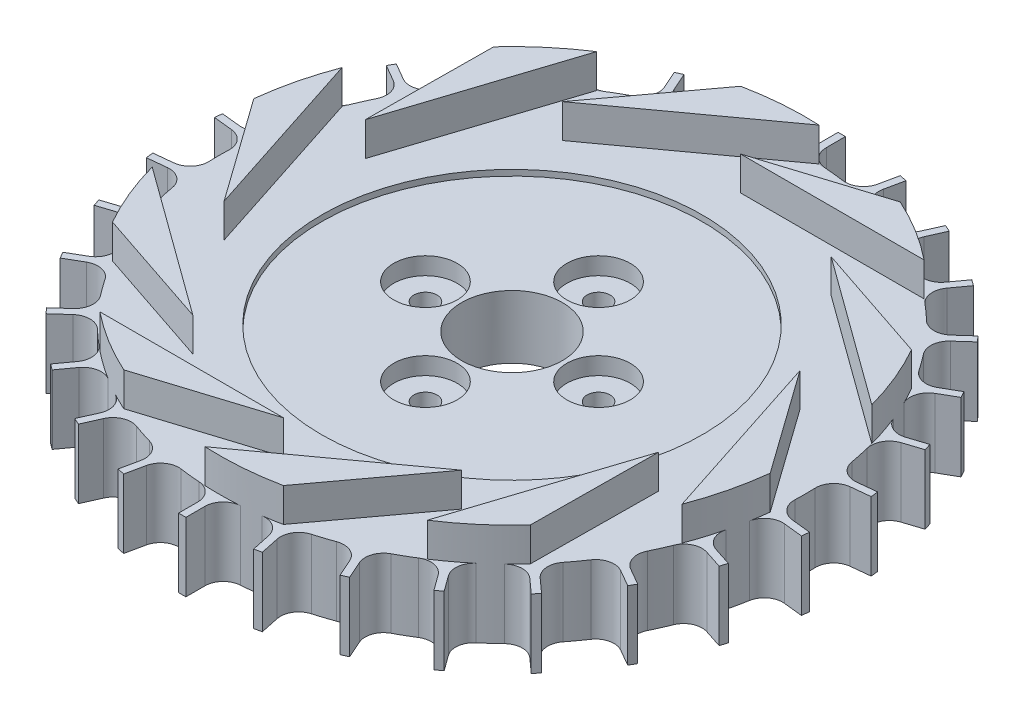
SolidWorks part; units mm, degrees
material "6061-T6 (SS)"
ref_plane "Front Plane" through (0, 0, 0) normal (0, 0, 1) x (1, 0, 0)
ref_plane "Top Plane" through (0, 0, 0) normal (0, 1, 0) x (1, 0, 0)
ref_plane "Right Plane" through (0, 0, 0) normal (1, 0, 0) x (0, 0, -1)
sketch "Sketch1" plane through (0, 0, 0) normal (1, 0, 0) x (0, 0, -1)
  line L0 (0, 26.2631) -> (0, -3.7705) construction
  line L1 (0, -3.7705) -> (-50.8, -3.7705)
  line L2 (-50.8, -3.7705) -> (-50.8, 8.1675)
  line L3 (-33.0001, 8.1675) -> (-50.8, 8.1675)
  line L4 (-33.0001, 8.1675) -> (-33.0001, 7.1515)
  line L5 (-33.0001, 7.1515) -> (0, 7.1515)
  line L6 (0, 7.1515) -> (0, -3.7705)
  dimension "D1" = 33.0001
  dimension "D2" = 50.8
  dimension "D3" = 1.016
  dimension "D4" = 11.938
revolve "Revolve1" add sketch "Sketch1" angle 360 about L0
sketch "Sketch2" plane through (0, 8.1675, 0) normal (0, 1, 0) x (1, 0, 0)
  line L8 (0, 39.6001) -> (19.9397, 39.6001) construction
  line L9 (0, 39.6001) -> (21.0453, 46.2356)
  line L10 (0, 39.6001) -> (31.8194, 39.6001)
  circle A0 centre (0, 0) radius 50.8 construction
  arc A3 (21.0453, 46.2356) -> (31.8194, 39.6001) centre (0, 0) cw
  circle A5 centre (0, 0) radius 33.0001 construction
  circle A7 centre (0, 0) radius 39.6001 construction
  point P9 (-2.4416, -40.4611)
  dimension "D1" = 66.0001
  dimension "D2" = 79.2001
  dimension "D3" = 17.5
extrude "Boss-Extrude1" add sketch "Sketch2" along normal blind 5.842
pattern_circular "CirPattern1" count 10 over 360 about axis through (0, 8.1675, 0) along (0, 1, 0) of "Boss-Extrude1"
ref_plane "Plane1" through (0, 0, 49.53) normal (0, 0, 1) x (1, 0, 0)
sketch "Sketch3" plane through (0, 0, 49.53) normal (0, 0, 1) x (1, 0, 0)
  line L0 (0, 0) -> (0, 9.7621) construction
  line L1 (0, -9.779) -> (0, 9.779) construction
  line L6 (-50.8, -3.7705) -> (50.8, -3.7705) construction
  line L13 (10.1506, 8.1675) -> (23.2763, 8.1675) construction
  line L14 (-0.635, -3.7705) -> (0.635, -3.7705)
  line L15 (-0.635, -3.7705) -> (-0.635, 8.1675)
  line L16 (-0.635, 8.1675) -> (0.635, 8.1675)
  line L17 (0.635, -3.7705) -> (0.635, 8.1675)
  point P11 (0, 8.1675)
  dimension "D1" = 1.27
extrude "Boss-Extrude2" add sketch "Sketch3" along normal blind 7.62 and the other way blind 0.254
fillet "Fillet1" radius 3.175 2 edges at (-0.635, 2.1985, 50.796) (0.635, 2.1985, 50.796)
pattern_circular "CirPattern16" count 30 over 360 about axis through (0, -3.7705, 0) along (0, 1, 0) of "Boss-Extrude2", "Fillet1"
sketch "Sketch4" plane through (0, 7.1515, 0) normal (0, 1, 0) x (1, 0, 0)
  circle A0 centre (0, 0) radius 8.7312
  dimension "D1" = 17.4625
extrude "Cut-Extrude1" cut sketch "Sketch4" against normal up to next
sketch "Sketch5" plane through (0, -3.7705, 0) normal (0, -1, 0) x (-1, 0, 0)
  circle A0 centre (0, 0) radius 44.45
  dimension "D1" = 88.9
extrude "Cut-Extrude2" cut sketch "Sketch5" against normal blind 6.35
sketch "Sketch6" plane through (0, 2.5795, 0) normal (0, -1, 0) x (1, 0, 0)
  circle A0 centre (0, 0) radius 19.05
  circle A1 centre (0, 0) radius 8.7312 construction
  circle A2 centre (0, 0) radius 8.7312
  dimension "D1" = 38.1
extrude "Boss-Extrude3" add sketch "Sketch6" along normal up to surface (6.35 mm away) up to face at (0, -3.7705, -44.45)
sketch "Sketch9" plane through (0, 7.1515, 0) normal (0, 1, 0) x (1, 0, 0)
  circle A0 centre (0, 15) radius 2
  dimension "D1" = 4
  dimension "D2" = 15
extrude "Cut-Extrude3" cut sketch "Sketch9" against normal up to next
pattern_circular "CirPattern17" count 4 over 360 about axis through (0, 7.1515, 0) along (0, 1, 0) of "Cut-Extrude3"
ref_plane "Plane2" through (51.9838, 0, -23.1447) normal (-0.9135, 0, 0.4067) x (0.4067, 0, 0.9135)
sketch "Sketch10" plane through (51.9838, 0, -23.1447) normal (-0.9135, 0, 0.4067) x (0.4067, 0, 0.9135)
  line L0 (3.175, -3.7705) -> (3.175, -0.5955)
  line L1 (-46.1462, -3.7705) -> (-41.4681, -3.7705) construction
  line L2 (-3.175, -0.5955) -> (-3.175, -3.7705)
  line L3 (-3.175, -3.7705) -> (3.175, -3.7705)
  arc A0 (3.175, -0.5955) -> (-3.175, -0.5955) centre (0, -0.5955) ccw
  dimension "D1" = 3.175
  dimension "D2" = 3.175
sketch "Sketch11" plane through (0, 7.1515, 0) normal (0, 1, 0) x (1, 0, 0)
  circle A0 centre (0, -15) radius 5.5
  circle A1 centre (-15, 0) radius 5.5
  circle A2 centre (0, 15) radius 5.5
  circle A3 centre (15, 0) radius 5.5
  dimension "D1" = 11
extrude "Cut-Extrude5" cut sketch "Sketch11" against normal blind 3
ref_plane "Plane3" through (0, 16.5495, 0) normal (0, 1, 0) x (1, 0, 0)
ref_axis "Axis4" through (0, -3.7705, 0) along (0, 1, 0)
ref_point "Point1"
